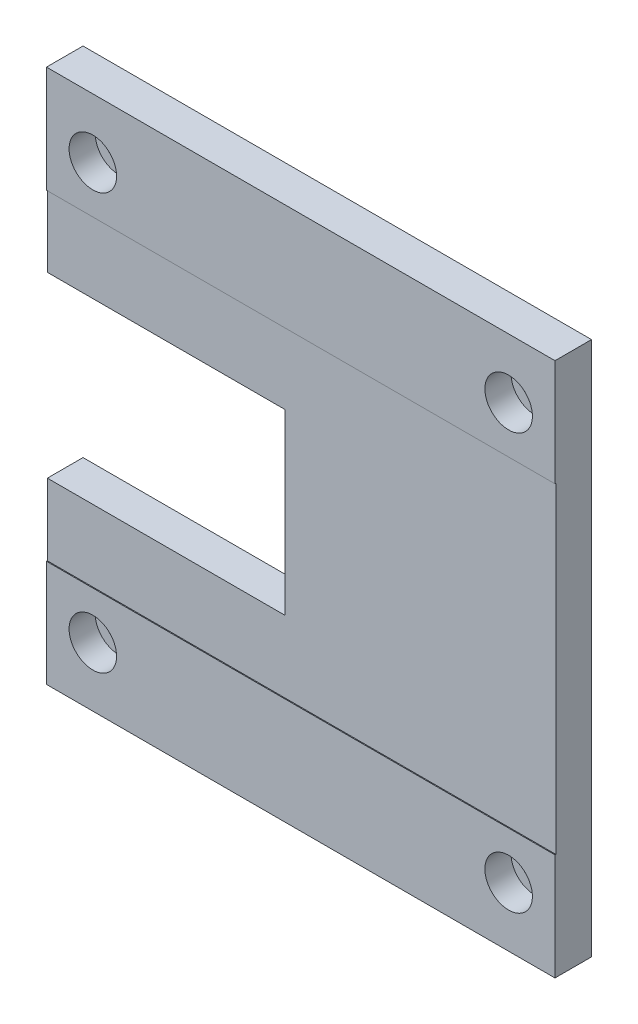
SolidWorks part; units mm, degrees
ref_plane "前视基准面" through (0, 0, 0) normal (0, 0, 1) x (1, 0, 0)
ref_plane "上视基准面" through (0, 0, 0) normal (0, 1, 0) x (1, 0, 0)
ref_plane "右视基准面" through (0, 0, 0) normal (1, 0, 0) x (0, 0, -1)
sketch "草图1" plane through (0, 0, 0) normal (0, 0, 1) x (1, 0, 0)
  line L1 (0, 0) -> (85.6, 0)
  line L2 (0, 0) -> (0, 90)
  line L3 (0, 90) -> (85.6, 90)
  line L4 (85.6, 0) -> (85.6, 90)
  dimension "D1" = 85.6
  dimension "D2" = 90
extrude "凸台-拉伸1" add sketch "草图1" along normal blind 6
sketch "草图2" plane through (0, 0, 6) normal (0, 0, 1) x (1, 0, 0)
  line L0 (0, 90) -> (0, 0) construction
  line L1 (85.6, 90) -> (0, 90)
  line L2 (85.6, 90) -> (85.6, 72.05)
  line L3 (85.6, 72.05) -> (0, 72.05)
  line L4 (0, 90) -> (0, 72.05)
  line L5 (42.8, 0) -> (42.8, 90) construction
  line L6 (0, 0) -> (85.6, 0) construction
  line L7 (42.8, 90) -> (42.8, 45) construction
  line L8 (42.8, 45) -> (71.9817, 45) construction
  line L9 (0, 0) -> (0, 17.95)
  line L10 (85.6, 17.95) -> (0, 17.95)
  line L11 (85.6, 0) -> (0, 0)
  line L12 (85.6, 0) -> (85.6, 17.95)
  dimension "D1" = 54.1
extrude "凸台-拉伸2" add sketch "草图2" along normal blind 0.15
sketch "草图3" plane through (0, 0, 6) normal (0, 0, 1) x (1, 0, 0)
  line L0 (0, 45) -> (112.2735, 45) construction
  line L1 (0, 72.05) -> (0, 17.95) construction
  line L3 (0, 60) -> (40, 60)
  line L4 (0, 60) -> (0, 30)
  line L5 (0, 30) -> (40, 30)
  line L6 (40, 60) -> (40, 30)
  dimension "D1" = 30
  dimension "D2" = 40
extrude "切除-拉伸1" cut sketch "草图3" against normal through all
hole_wizard "M4 六角凹头螺钉的柱形沉头孔1" positions "草图6" profile "草图7" counterbore size "M4" standard "ISO" end condition through all
sketch "草图6" plane through (0, 0, 6.15) normal (0, 0, 1) x (1, 0, 0)
  line L0 (42.8, 90) -> (42.8, 0) construction
  line L1 (85.6, 90) -> (0, 90) construction
  line L2 (0, 0) -> (85.6, 0) construction
  line L3 (42.8, 0) -> (42.8, 45) construction
  line L4 (42.8, 45) -> (-12.8672, 45) construction
  point P0 (77.8, 80)
  point P14 (7.8, 80)
  point P15 (7.8, 10)
  point P16 (77.8, 10)
  dimension "D1" = 70
  dimension "D2" = 70
sketch "草图7" plane through (77.8, 80, 6.15) normal (1, 0, 0) x (0, -1, 0)
  line L0 (0, 0) -> (0, 6.15)
  line L1 (0, 6.15) -> (2.25, 6.15)
  line L3 (2.25, 6.15) -> (2.25, 4.4)
  line L4 (2.25, 4.4) -> (4, 4.4)
  line L5 (4, 4.4) -> (4, 0)
  line L7 (4, 0) -> (0, 0)
  line L11 (0, -6.35) -> (0, 107.95) construction
  dimension "通孔孔直径" = 4.5
  dimension "通孔孔深度" = 6.15
  dimension "柱形沉头孔直径" = 8
  dimension "柱形沉头孔深度" = 4.4
